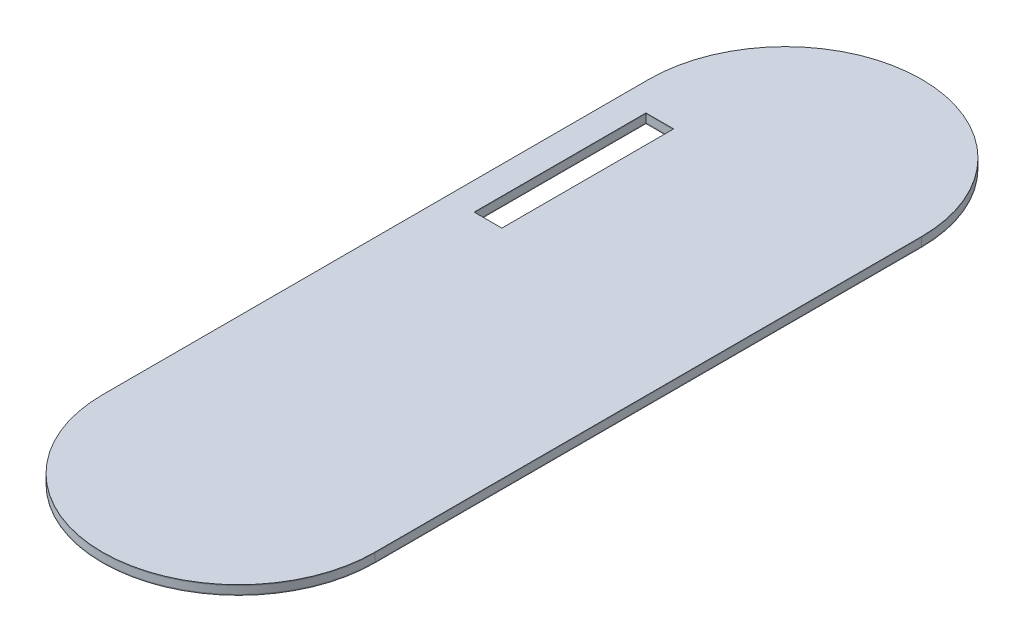
SolidWorks part; units mm, degrees
ref_plane "Front Plane" through (0, 0, 0) normal (0, 0, 1) x (1, 0, 0)
ref_plane "Top Plane" through (0, 0, 0) normal (0, 1, 0) x (1, 0, 0)
ref_plane "Right Plane" through (0, 0, 0) normal (1, 0, 0) x (0, 0, -1)
sketch "Sketch1" plane through (0, 0, 0) normal (0, 1, 0) x (1, 0, 0)
  line L0 (0, -88.9) -> (0, 88.9) construction
  line L2 (44.323, 88.9) -> (44.323, -88.9)
  line L8 (-35.323, 23.02) -> (-35.323, 78.9)
  line L11 (-35.323, 78.9) -> (-26.323, 78.9)
  line L12 (-26.323, 78.9) -> (-26.323, 23.02)
  line L13 (-26.323, 23.02) -> (-35.323, 23.02)
  line L14 (-44.323, 88.9) -> (-44.323, -88.9)
  arc A0 (44.323, 88.9) -> (-44.323, 88.9) centre (0, 88.9) ccw
  arc A1 (-44.323, -88.9) -> (44.323, -88.9) centre (0, -88.9) ccw
  point P8 (0, 0)
  point P13 (-89.4761, 0)
  point P18 (-35.323, 50.96)
  dimension "D2" = 88.646
  dimension "D1" = 177.8
  dimension "D3" = 55.88
  dimension "D4" = 9
  dimension "D5" = 10
  dimension "D6" = 9
extrude "Boss-Extrude1" add sketch "Sketch1" along normal blind 0.25
sketch "Sketch2" plane through (0, 0.25, 0) normal (0, 1, 0) x (1, 0, 0)
  line L0 (-26.323, 78.9) -> (-35.323, 78.9) construction
  line L1 (-35.323, 78.9) -> (-35.323, 23.02) construction
  line L2 (-44.323, 88.9) -> (-44.323, -88.9)
  line L3 (44.323, -88.9) -> (44.323, 88.9)
  line L4 (-44.323, 88.9) -> (-44.323, -88.9)
  line L5 (44.323, -88.9) -> (44.323, 88.9)
  line L6 (-35.323, 23.02) -> (-26.323, 23.02) construction
  line L7 (-26.323, 23.02) -> (-26.323, 78.9) construction
  line L8 (-26.323, 78.9) -> (-35.323, 78.9)
  line L9 (-35.323, 78.9) -> (-35.323, 23.02)
  line L10 (-35.323, 23.02) -> (-26.323, 23.02)
  line L11 (-26.323, 23.02) -> (-26.323, 78.9)
  arc A2 (44.323, 88.9) -> (-44.323, 88.9) centre (0, 88.9) ccw
  arc A3 (-44.323, -88.9) -> (44.323, -88.9) centre (0, -88.9) ccw
  arc A4 (44.323, 88.9) -> (-44.323, 88.9) centre (0, 88.9) ccw
  arc A5 (-44.323, -88.9) -> (44.323, -88.9) centre (0, -88.9) ccw
  arc M5 (44.323, 88.9) -> (-44.323, 88.9) centre (0, 88.9) ccw
  line M6 (-44.323, 88.9) -> (-44.323, -88.9)
  arc M7 (-44.323, -88.9) -> (44.323, -88.9) centre (0, -88.9) ccw
  line M8 (44.323, -88.9) -> (44.323, 88.9)
  line M9 (-35.323, 78.9) -> (-26.323, 78.9)
  line M10 (-26.323, 78.9) -> (-26.323, 23.02)
  line M11 (-26.323, 23.02) -> (-35.323, 23.02)
  line M12 (-35.323, 23.02) -> (-35.323, 78.9)
  dimension "D1" = 0
extrude "Boss-Extrude3" add sketch "Sketch2" along normal blind 2.5 separate body contours M8 M5 M6 M7 M12 M9 M10 M11 region at (0.7234, 0.25, 1.1959)
sketch "Sketch3" plane through (0, 2.75, 0) normal (0, 1, 0) x (1, 0, 0)
  line L4 (-35.323, 78.9) -> (-35.323, 23.02)
  line L5 (-26.323, 78.9) -> (-35.323, 78.9)
  line L6 (-26.323, 23.02) -> (-26.323, 78.9)
  line L7 (-35.323, 23.02) -> (-26.323, 23.02)
  line L8 (-35.323, 78.9) -> (-35.323, 23.02)
  line L9 (-26.323, 78.9) -> (-35.323, 78.9)
  line L10 (-26.323, 23.02) -> (-26.323, 78.9)
  line L11 (-35.323, 23.02) -> (-26.323, 23.02)
  line M5 (-35.323, 23.02) -> (-35.323, 78.9)
  line M6 (-35.323, 78.9) -> (-26.323, 78.9)
  line M7 (-26.323, 78.9) -> (-26.323, 23.02)
  line M8 (-26.323, 23.02) -> (-35.323, 23.02)
  line M9 (44.323, -88.9) -> (44.323, 88.9)
  arc M10 (44.323, 88.9) -> (-44.323, 88.9) centre (0, 88.9) ccw
  line M11 (-44.323, 88.9) -> (-44.323, -88.9)
  arc M12 (-44.323, -88.9) -> (44.323, -88.9) centre (0, -88.9) ccw
  dimension "D1" = 0
extrude "Boss-Extrude4" add sketch "Sketch3" along normal blind 0.25 separate body contours M12 M9 M10 M11 M8 M5 M6 M7 region at (0.7234, 2.75, 1.1959)
